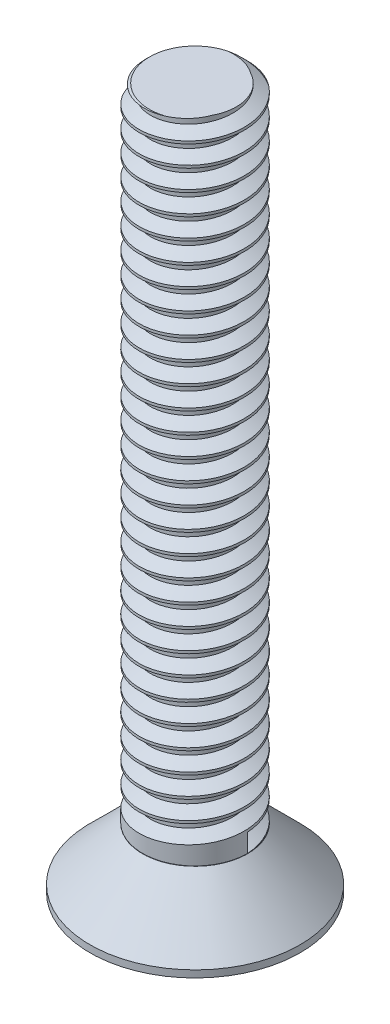
SolidWorks part; units mm, degrees
material "Galvanized Steel"
ref_plane "Front Plane" through (0, 0, 0) normal (0, 0, 1) x (1, 0, 0)
ref_plane "Top Plane" through (0, 0, 0) normal (0, 1, 0) x (1, 0, 0)
ref_plane "Right Plane" through (0, 0, 0) normal (1, 0, 0) x (0, 0, -1)
sketch "Sketch1" plane through (0, 0, 0) normal (0, 0, 1) x (1, 0, 0)
  line L0 (0, 0) -> (0, 13.3573) construction
  line L1 (0, 1.9261) -> (-3, 1.9261)
  line L2 (-3, 1.9261) -> (-3, 2.1261)
  line L3 (-1.5, 21.9261) -> (0, 21.9261)
  line L4 (-1.5, 3.6361) -> (-1.5, 21.9261)
  line L5 (-3, 2.1261) -> (-1.5, 3.6261)
  line L7 (0, 1.9261) -> (0, 21.9261)
  line L8 (-1.5, 3.6361) -> (-1.49, 3.6361)
  line L10 (-1.5, 3.6261) -> (-1.49, 3.6261)
  line L18 (-1.49, 3.6261) -> (-1.49, 3.6361)
  point P9 (-1.5, 9.9261)
  point P12 (-1.49, 3.622)
  point P13 (-1.49, 9.9161)
  point P16 (0, 3.6361)
  dimension "D1" = 0.01
  dimension "dk" = 6
  dimension "c" = 0.2
  dimension "k" = 1.7
  dimension "d" = 3
  dimension "l" = 20
revolve "Revolve1" add sketch "Sketch1" angle 360 about L0
chamfer "Chamfer1" distance 0.2 angle 45 1 edges at (0, 21.9261, -1.5)
sketch "Sketch2" plane through (0, 1.9261, 0) normal (0, -1, 0) x (1, 0, 0)
  line L1 (1.1547, 0) -> (0.5774, 1)
  line L2 (0.5774, 1) -> (-0.5774, 1)
  line L3 (-0.5774, 1) -> (-1.1547, 0)
  line L4 (-1.1547, 0) -> (-0.5774, -1)
  line L5 (-0.5774, -1) -> (0.5774, -1)
  line L6 (0.5774, -1) -> (1.1547, 0)
  circle A0 centre (0, 0) radius 1 construction
  dimension "s" = 2
extrude "hex depth" cut sketch "Sketch2" against normal blind 1.2
sketch "Sketch3" plane through (0, 1.9261, 0) normal (0, -1, 0) x (1, 0, 0)
  circle A0 centre (0, 0) radius 1.1547
ref_plane "Plane1" through (0, 2.1261, 0) normal (0, 1, 0) x (1, 0, 0)
sketch "Sketch4" plane through (0, 2.1261, 0) normal (0, 1, 0) x (1, 0, 0)
  circle A0 centre (0, 0) radius 1
loft "hex corner cut" cut profiles "Sketch4", "Sketch3"
thread "threadM3" pitch 0.6 profile "Thread Profile2" start angle 0, offset 0, length 0, pitch 0.6, diameter 3
ref_plane "Plane3" through (1.5, 3.6361, 0) normal (0, 0, 1) x (1, 0, 0)
sketch "Thread Profile2" plane through (1.5, 3.6361, 0) normal (0, 0, 1) x (1, 0, 0)
  line L0 (0, 0) -> (0, 0.6) construction
  line L11 (0, 0) -> (0, 0.525)
  line L12 (0, 0.525) -> (-0.3248, 0.3375)
  line L13 (-0.3248, 0.3375) -> (-0.3248, 0.1875)
  line L15 (-0.3248, 0.1875) -> (0, 0)
  line L17 (-0.3248, 0.2625) -> (0, 0.2625) construction
  point P2 (0, 0)
  dimension "Pitch" = 0.6
  dimension "Profile_Angle" = 60
  dimension "Profile_Land" = 0.15
  dimension "Profile_Height" = 0.3248
